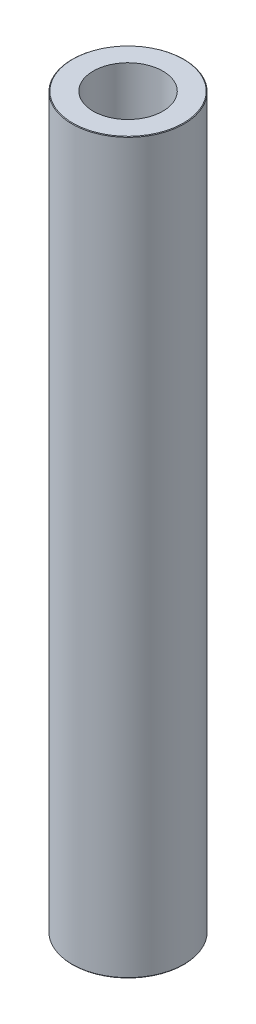
SolidWorks part; units mm, degrees
ref_plane "Front Plane" through (0, 0, 0) normal (0, 0, 1) x (1, 0, 0)
ref_plane "Top Plane" through (0, 0, 0) normal (0, 1, 0) x (1, 0, 0)
ref_plane "Right Plane" through (0, 0, 0) normal (1, 0, 0) x (0, 0, -1)
sketch "Sketch1" plane through (0, 0, 0) normal (0, 1, 0) x (1, 0, 0)
  circle A0 centre (0, 0) radius 35
  dimension "SHAFT_OD" = 70
extrude "Boss-Extrude1" add sketch "Sketch1" along normal blind 455.6186
sketch "Sketch2" plane through (0, 0, 0) normal (0, 1, 0) x (1, 0, 0)
  circle A0 centre (0, 0) radius 21.7673
  dimension "BORE_D" = 43.5346
extrude "Cut-Extrude1" cut sketch "Sketch2" along normal through all
chamfer "Chamfer1" distance 0.308 angle 53.087 2 edges at (0, 455.6186, 35) (0, 0, 35) first distance on face at (0, 455.6186, 35) first distance on face at (0, 0, 21.7673)
